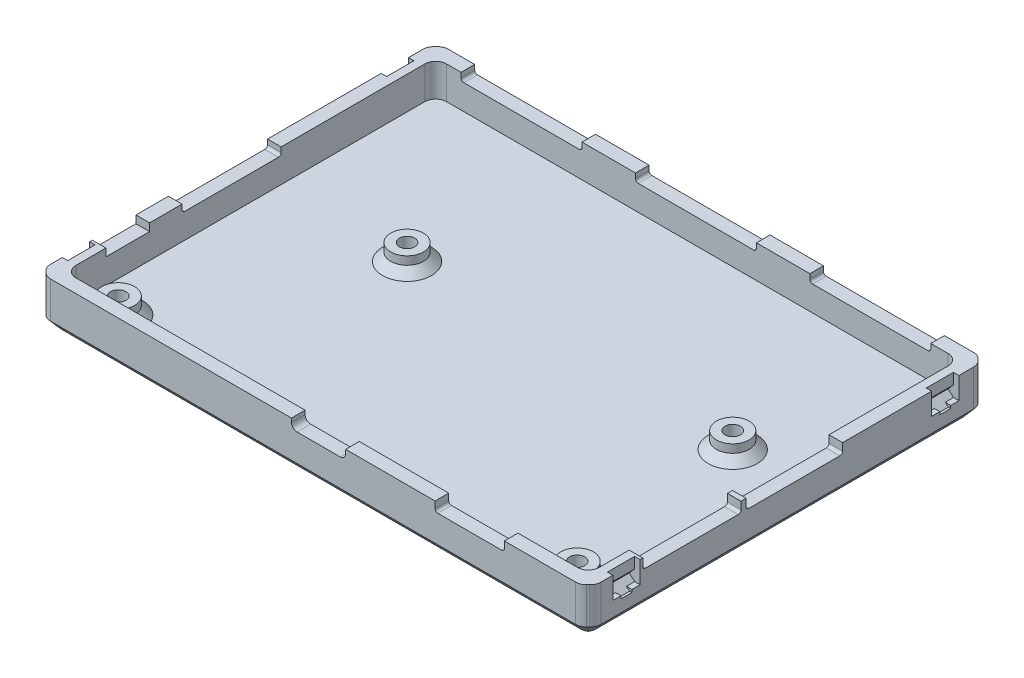
SolidWorks part; units mm, degrees
ref_plane "Front Plane" through (0, 0, 0) normal (0, 0, 1) x (1, 0, 0)
ref_plane "Top Plane" through (0, 0, 0) normal (0, 1, 0) x (1, 0, 0)
ref_plane "Right Plane" through (0, 0, 0) normal (1, 0, 0) x (0, 0, -1)
sketch "Sketch1" plane through (0, 0, 0) normal (0, 1, 0) x (1, 0, 0)
  line L1 (-50.5, -36.5) -> (50.5, -36.5)
  line L2 (-50.5, -36.5) -> (-50.5, 36.5)
  line L3 (-50.5, 36.5) -> (50.5, 36.5)
  line L4 (50.5, -36.5) -> (50.5, 36.5)
  line L5 (-50.5, -36.5) -> (50.5, 36.5) construction
  line L6 (-50.5, 36.5) -> (50.5, -36.5) construction
  point P0 (0, 0)
  dimension "D1" = 101
  dimension "D2" = 73
extrude "Boss-Extrude1" add sketch "Sketch1" along normal blind 8.5
shell "Shell1" thickness 2.5 removed face at (0, 8.5, 0)
sketch "Sketch5" plane through (0, 0, 36.5) normal (0, 0, 1) x (1, 0, 0)
  line L5 (-50.5, 8.5) -> (50.5, 8.5) construction
  line L6 (-3.96, 8.5) -> (5.98, 8.5)
  line L7 (-3.96, 8.5) -> (-3.96, 6.8)
  line L9 (-3.96, 6.8) -> (5.98, 6.8)
  line L10 (5.98, 8.5) -> (5.98, 6.8)
  line L11 (-3.96, 8.5) -> (5.98, 6.8) construction
  line L12 (-3.96, 6.8) -> (5.98, 8.5) construction
  line L13 (-3.46, 9.18) -> (-3.46, 8.58) construction
  line L14 (5.48, 9.18) -> (5.48, 8.58) construction
  point P4 (1.01, 7.65)
  dimension "D1" = 0.5
  dimension "D2" = 0.5
  dimension "D3" = 1.7
extrude "Cut-Extrude1" cut sketch "Sketch5" against normal blind 10
sketch "Sketch6" plane through (0, 0, 36.5) normal (0, 0, 1) x (1, 0, 0)
  line L0 (5.98, 8.5) -> (50.5, 8.5) construction
  line L1 (22.394, 8.5) -> (35.094, 8.5)
  line L2 (22.394, 8.5) -> (22.394, 6.79)
  line L3 (22.394, 6.79) -> (35.094, 6.79)
  line L4 (35.094, 8.5) -> (35.094, 6.79)
  line L5 (22.394, 8.5) -> (35.094, 6.79) construction
  line L6 (22.394, 6.79) -> (35.094, 8.5) construction
  line L7 (22.894, 7.59) -> (22.894, 11.1657) construction
  line L8 (34.594, 7.59) -> (34.594, 11.1657) construction
  point P4 (28.744, 7.645)
  dimension "D1" = 0.5
  dimension "D2" = 0.5
  dimension "D3" = 1.71
extrude "Cut-Extrude2" cut sketch "Sketch6" against normal blind 10
sketch "Sketch7" plane through (50.5, 0, 0) normal (1, 0, 0) x (0, 0, -1)
  line L0 (-36.5, 8.5) -> (36.5, 8.5) construction
  line L1 (-26.5, 8.5) -> (-8.4735, 8.5)
  line L2 (-26.5, 8.5) -> (-26.5, 6.65)
  line L3 (-26.5, 6.65) -> (-8.4735, 6.65)
  line L4 (-8.4735, 8.5) -> (-8.4735, 6.65)
  line L5 (-26.5, 8.5) -> (-8.4735, 6.65) construction
  line L6 (-26.5, 6.65) -> (-8.4735, 8.5) construction
  line L7 (-26, 7.15) -> (-26, 16.35) construction
  line L8 (-7.536, 8.5) -> (10.164, 8.5)
  line L9 (-7.536, 8.5) -> (-7.536, 6.65)
  line L10 (-7.536, 6.65) -> (10.164, 6.65)
  line L11 (10.164, 8.5) -> (10.164, 6.65)
  line L12 (-7.536, 8.5) -> (10.164, 6.65) construction
  line L13 (-7.536, 6.65) -> (10.164, 8.5) construction
  line L14 (-8.9735, 7.45) -> (-8.9735, 11.0257) construction
  line L15 (-7.036, 7.45) -> (-7.036, 11.0257) construction
  line L16 (9.664, 7.45) -> (9.664, 11.0257) construction
  point P4 (-17.4867, 7.575)
  point P11 (1.314, 7.575)
  dimension "D1" = 0.5
  dimension "D2" = 0.5
  dimension "D3" = 0.5
  dimension "D4" = 0.5
  dimension "D5" = 1.85
  dimension "D6" = 1.85
extrude "Cut-Extrude3" cut sketch "Sketch7" against normal blind 10
sketch "Sketch8" plane through (0, 0, -36.5) normal (0, 0, -1) x (-1, 0, 0)
  line L0 (-50.5, 8.5) -> (50.5, 8.5) construction
  line L1 (-42.84, 8.5) -> (-20.66, 8.5)
  line L2 (-42.84, 8.5) -> (-42.84, 7.1)
  line L3 (-42.84, 7.1) -> (-20.66, 7.1)
  line L4 (-20.66, 8.5) -> (-20.66, 7.1)
  line L5 (-42.84, 8.5) -> (-20.66, 7.1) construction
  line L6 (-42.84, 7.1) -> (-20.66, 8.5) construction
  line L7 (21.66, 7.33) -> (21.66, 8.71) construction
  line L8 (-10.84, 8.5) -> (11.34, 8.5)
  line L9 (-10.84, 8.5) -> (-10.84, 7.1)
  line L10 (-10.84, 7.1) -> (11.34, 7.1)
  line L11 (11.34, 8.5) -> (11.34, 7.1)
  line L12 (-10.84, 8.5) -> (11.34, 7.1) construction
  line L13 (-10.84, 7.1) -> (11.34, 8.5) construction
  line L14 (21.16, 8.5) -> (43.34, 8.5)
  line L15 (21.16, 8.5) -> (21.16, 7.1)
  line L16 (21.16, 7.1) -> (43.34, 7.1)
  line L17 (43.34, 8.5) -> (43.34, 7.1)
  line L18 (21.16, 8.5) -> (43.34, 7.1) construction
  line L19 (21.16, 7.1) -> (43.34, 8.5) construction
  line L20 (42.84, 7.33) -> (42.84, 8.71) construction
  line L21 (10.84, 7.33) -> (10.84, 8.71) construction
  line L22 (-10.34, 7.33) -> (-10.34, 8.71) construction
  line L23 (-42.34, 7.33) -> (-42.34, 8.71) construction
  line L24 (-21.16, 7.33) -> (-21.16, 8.71) construction
  point P4 (-31.75, 7.8)
  point P11 (0.25, 7.8)
  point P16 (32.25, 7.8)
  dimension "D1" = 0.5
  dimension "D2" = 0.5
  dimension "D3" = 1.4
  dimension "D4" = 0.5
  dimension "D5" = 0.5
  dimension "D6" = 0.5
  dimension "D7" = 0.5
  dimension "D8" = 1.4
  dimension "D9" = 1.4
extrude "Cut-Extrude4" cut sketch "Sketch8" against normal blind 10
sketch "Sketch9" plane through (-50.5, 0, 0) normal (-1, 0, 0) x (0, 0, 1)
  line L0 (-36.5, 8.5) -> (36.5, 8.5) construction
  line L1 (-5.64, 8.5) -> (12.54, 8.5)
  line L2 (-5.64, 8.5) -> (-5.64, 7.1)
  line L3 (-5.64, 7.1) -> (12.54, 7.1)
  line L4 (12.54, 8.5) -> (12.54, 7.1)
  line L5 (-5.64, 8.5) -> (12.54, 7.1) construction
  line L6 (-5.64, 7.1) -> (12.54, 8.5) construction
  line L8 (12.04, 7.33) -> (12.04, 8.71) construction
  line L9 (-5.14, 7.33) -> (-5.14, 8.71) construction
  point P4 (3.45, 7.8)
  dimension "D1" = 0.5
  dimension "D2" = 0.5
  dimension "D3" = 1.4
extrude "Cut-Extrude5" cut sketch "Sketch9" against normal blind 10
sketch "Sketch10" plane through (-50.5, 0, 0) normal (-1, 0, 0) x (0, 0, 1)
  line L0 (12.54, 8.5) -> (36.5, 8.5) construction
  line L1 (18.5, 8.5) -> (26.5, 8.5)
  line L2 (18.5, 8.5) -> (18.5, 7.1)
  line L3 (18.5, 7.1) -> (26.5, 7.1)
  line L4 (26.5, 8.5) -> (26.5, 7.1)
  line L5 (18.5, 8.5) -> (26.5, 7.1) construction
  line L6 (18.5, 7.1) -> (26.5, 8.5) construction
  line L7 (19, 10) -> (19, 7.15) construction
  line L8 (26, 10) -> (26, 7.15) construction
  point P4 (22.5, 7.8)
  point P7 (18.5, 7.8)
  dimension "D1" = 1.4
  dimension "D2" = 0.5
  dimension "D3" = 0.5
extrude "Cut-Extrude6" cut sketch "Sketch10" against normal blind 10
fillet "Fillet1" radius 2 4 edges at (-48, 5.5, -34) (48, 5.5, -34) (48, 5.5, 34) (-48, 5.5, 34)
sketch "Sketch11" plane through (0, 2.5, 0) normal (0, 1, 0) x (1, 0, 0)
  circle A0 centre (35.5, 5) radius 3
  circle A1 centre (42, -30.05) radius 3
  circle A2 centre (-42.25, -30) radius 3
  circle A3 centre (-24.25, 5) radius 3
  dimension "D1" = 6
extrude "Boss-Extrude3" add sketch "Sketch11" along normal blind 3
sketch "Sketch12" plane through (0, 5.5, 0) normal (0, 1, 0) x (1, 0, 0)
  circle A0 centre (-42.25, -30) radius 1.4
  circle A1 centre (-24.25, 5) radius 1.4
  circle A2 centre (35.5, 5) radius 1.4
  circle A3 centre (42, -30.05) radius 1.4
  dimension "D1" = 2.8
extrude "Boss-Extrude4" add sketch "Sketch12" against normal up to surface (3 mm away) up to face at (-24.25, 2.5, -8)
chamfer "Chamfer1" distance 1.5 angle 45 4 edges at (-42.25, 2.5, 27) (-24.25, 2.5, -8) (35.5, 2.5, -8) (42, 2.5, 27.05)
chamfer "Chamfer2" distance 1.5 angle 45 4 edges at (-50.5, 4.25, -36.5) (50.5, 4.25, -36.5) (50.5, 4.25, 36.5) (-50.5, 4.25, 36.5)
chamfer "Chamfer3" distance 1.5 angle 50 8 edges at (-49.75, 0, 35.75) (0, 0, 36.5) (49.75, 0, 35.75) (50.5, 0, 0) (49.75, 0, -35.75) (0, 0, -36.5) (-49.75, 0, -35.75) (-50.5, 0, 0) first distance on face at (0, 0, 0)
fillet "Fillet3" radius 2 8 edges at (-50.5, 5.1438, -35) (-49, 5.1438, -36.5) (49, 5.1438, -36.5) (50.5, 5.1438, -35) (50.5, 5.1438, 35) (49, 5.1438, 36.5) (-50.5, 5.1438, 35) (-49, 5.1438, 36.5)
fillet "Fillet4" radius 2.6 8 edges at (49.6739, 0.8031, 34.6578) (48.6578, 0.8031, 35.6739) (-48.6578, 0.8031, 35.6739) (-49.6739, 0.8031, 34.6578) (-48.6578, 0.8031, -35.6739) (-49.6739, 0.8031, -34.6578) (49.6739, 0.8031, -34.6578) (48.6578, 0.8031, -35.6739)
sketch "Sketch14" plane through (0, 5.5, 0) normal (0, 1, 0) x (1, 0, 0)
  circle A0 centre (-24.25, 5) radius 1.4
  circle A1 centre (-42.25, -30) radius 1.4
  circle A2 centre (35.5, 5) radius 1.4
  circle A3 centre (42, -30.05) radius 1.4
  dimension "D1" = 2.8
extrude "Cut-Extrude7" cut sketch "Sketch14" against normal up to surface (3 mm away) up to face at (-24.25, 2.5, -9.5)
fillet "Fillet5" radius 1 2 edges at (5.98, 6.8, 35.25) (-3.96, 6.8, 35.25)
fillet "Fillet6" radius 0.5 2 edges at (35.094, 6.79, 35.25) (22.394, 6.79, 35.25)
fillet "Fillet7" radius 0.5 12 edges at (-49.25, 7.1, 12.54) (-49.25, 7.1, -5.64) (-43.34, 7.1, -35.25) (-21.16, 7.1, -35.25) (-11.34, 7.1, -35.25) (10.84, 7.1, -35.25) (20.66, 7.1, -35.25) (42.84, 7.1, -35.25) (49.25, 6.65, -10.164) (49.25, 6.65, 7.536) (49.25, 6.65, 8.4735) (49.25, 6.65, 26.5)
ref_plane "Plane1" through (0, 0, -31.5) normal (0, 0, 1) x (1, 0, 0)
sketch "Sketch16" plane through (0, 0, -31.5) normal (0, 0, 1) x (1, 0, 0)
  line L0 (-49.5, 6.5) -> (-48.5078, 5.375)
  line L1 (-48.5078, 5.375) -> (-49.5, 4.5)
  line L2 (-49.5, 4.5) -> (-49.5, 6.5)
  line L3 (50.5, 8.5) -> (48, 8.5) construction
  line L5 (49.5, 6.5) -> (49.5, 4.5)
  line L6 (49.5, 4.5) -> (48.5078, 5.375)
  line L7 (48.5078, 5.375) -> (49.5, 6.5)
  line L8 (-50.5, 8.5) -> (-49.5, 8.5)
  line L9 (-50.5, 8.5) -> (-48, 8.5) construction
  line L10 (-48, 2.5) -> (-48, 8.5) construction
  line L11 (-50.5, 8.5) -> (-50.5, 4.5)
  line L12 (-50.5, 4.5) -> (-49.5, 4.5)
  line L13 (-49.5, 8.5) -> (-49.5, 4.5)
  line L14 (-50.5, 8.5) -> (-49.5, 4.5) construction
  line L15 (-50.5, 4.5) -> (-49.5, 8.5) construction
  line L16 (50.5, 8.5) -> (49.5, 8.5)
  line L17 (50.5, 8.5) -> (50.5, 4.5)
  line L18 (50.5, 4.5) -> (49.5, 4.5)
  line L19 (49.5, 8.5) -> (49.5, 4.5)
  line L20 (50.5, 8.5) -> (49.5, 4.5) construction
  line L21 (50.5, 4.5) -> (49.5, 8.5) construction
  point P16 (-50, 6.5)
  point P21 (50, 6.5)
  dimension "D1" = 1
  dimension "D2" = 2
  dimension "D3" = 1.5
  dimension "D4" = 4
  dimension "D5" = 2
  dimension "D6" = 1.5
  dimension "D7" = 41.41
  dimension "D8" = 4
  dimension "D9" = 1
extrude "Cut-Extrude8" cut sketch "Sketch16" along normal blind 5 contours L7 L6 L5 | L16 L19 L5 L18 L17 | L2 L1 L0 | L13 L8 L11 L12 L2 region at (-49.1693, 5.4583, -31.5) region at (-50, 6.5, -31.5) region at (50, 6.5, -31.5) region at (49.1693, 5.4583, -31.5)
ref_plane "Plane2" through (0, 0, 32) normal (0, 0, -1) x (-1, 0, 0)
sketch "Sketch17" plane through (0, 0, 32) normal (0, 0, -1) x (-1, 0, 0)
  line L0 (-50.5, 8.5) -> (-48, 8.5) construction
  line L3 (-49.5, 6.5) -> (-48.5078, 5.375)
  line L4 (-50.5, 8.5) -> (-49.5, 8.5)
  line L5 (-50.5, 8.5) -> (-50.5, 4.5)
  line L6 (-50.5, 4.5) -> (-49.5, 4.5)
  line L7 (-49.5, 8.5) -> (-49.5, 4.5)
  line L8 (-50.5, 8.5) -> (-49.5, 4.5) construction
  line L9 (-50.5, 4.5) -> (-49.5, 8.5) construction
  line L10 (-48.5078, 5.375) -> (-49.5, 4.5)
  line L11 (50.5, 8.5) -> (48, 8.5) construction
  line L12 (49.5, 6.5) -> (48.5078, 5.375)
  line L13 (50.5, 8.5) -> (49.5, 8.5)
  line L14 (50.5, 8.5) -> (50.5, 4.5)
  line L15 (50.5, 4.5) -> (49.5, 4.5)
  line L16 (49.5, 8.5) -> (49.5, 4.5)
  line L17 (50.5, 8.5) -> (49.5, 4.5) construction
  line L18 (50.5, 4.5) -> (49.5, 8.5) construction
  line L19 (48.5078, 5.375) -> (49.5, 4.5)
  point P9 (-50, 6.5)
  point P18 (50, 6.5)
  dimension "D1" = 1
  dimension "D2" = 4
  dimension "D3" = 1.5
  dimension "D4" = 41.41
  dimension "D5" = 2
  dimension "D6" = 4
  dimension "D7" = 1
  dimension "D8" = 2
  dimension "D9" = 1.5
  dimension "D10" = 41.41
extrude "Cut-Extrude9" cut sketch "Sketch17" along normal blind 5 contours L13 L16 L15 L14 | L12 L19 L16 | L7 L4 L5 L6 | L10 L3 L7 region at (50, 6.5, 32) region at (49.1693, 5.4583, 32) region at (-49.1693, 5.4583, 32) region at (-50, 6.5, 32)
sketch "Sketch18" plane through (-50.5, 0, 0) normal (-1, 0, 0) x (0, 0, 1)
  line L0 (-26.5, 4.5) -> (-31.5, 4.5) construction
  line L1 (-30, 4.5) -> (-28, 4.5)
  line L2 (-30, 4.5) -> (-30, 4)
  line L3 (-30, 4) -> (-28, 4)
  line L4 (-28, 4.5) -> (-28, 4)
  line L5 (-30, 4.5) -> (-28, 4) construction
  line L6 (-30, 4) -> (-28, 4.5) construction
  line L13 (-31.5, 8.5) -> (-31.5, 4.5) construction
  line L14 (27, 4.5) -> (32, 4.5) construction
  line L15 (28.5, 4.5) -> (30.5, 4.5)
  line L16 (28.5, 4.5) -> (28.5, 4)
  line L17 (28.5, 4) -> (30.5, 4)
  line L18 (30.5, 4.5) -> (30.5, 4)
  line L19 (28.5, 4.5) -> (30.5, 4) construction
  line L20 (28.5, 4) -> (30.5, 4.5) construction
  line L21 (27, 8.5) -> (27, 4.5) construction
  point P4 (-29, 4.25)
  point P13 (29.5, 4.25)
  dimension "D1" = 2
  dimension "D2" = 0.5
  dimension "D3" = 2.5
  dimension "D4" = 0.5
  dimension "D5" = 2
  dimension "D6" = 2.5
extrude "Cut-Extrude10" cut sketch "Sketch18" against normal up to surface (1 mm away) up to face at (-49.0039, 4.9375, 29.5)
sketch "Sketch19" plane through (50.5, 0, 0) normal (1, 0, 0) x (0, 0, -1)
  line L0 (-27, 4.5) -> (-32, 4.5) construction
  line L1 (-30.5, 4.5) -> (-28.5, 4.5)
  line L2 (-30.5, 4.5) -> (-30.5, 4)
  line L3 (-30.5, 4) -> (-28.5, 4)
  line L4 (-28.5, 4.5) -> (-28.5, 4)
  line L5 (-30.5, 4.5) -> (-28.5, 4) construction
  line L6 (-30.5, 4) -> (-28.5, 4.5) construction
  line L7 (26.5, 4.5) -> (31.5, 4.5) construction
  line L8 (28, 4.5) -> (30, 4.5)
  line L9 (28, 4.5) -> (28, 4)
  line L10 (28, 4) -> (30, 4)
  line L11 (30, 4.5) -> (30, 4)
  line L12 (28, 4.5) -> (30, 4) construction
  line L13 (28, 4) -> (30, 4.5) construction
  line L14 (26.5, 8.5) -> (26.5, 4.5) construction
  line L15 (-32, 8.5) -> (-32, 4.5) construction
  point P4 (-29.5, 4.25)
  point P11 (29, 4.25)
  dimension "D1" = 2
  dimension "D2" = 2.5
  dimension "D3" = 0.5
  dimension "D4" = 2
  dimension "D5" = 2.5
  dimension "D6" = 0.5
extrude "Cut-Extrude11" cut sketch "Sketch19" against normal up to surface (1 mm away) up to face at (49.0039, 4.9375, 29.5)
